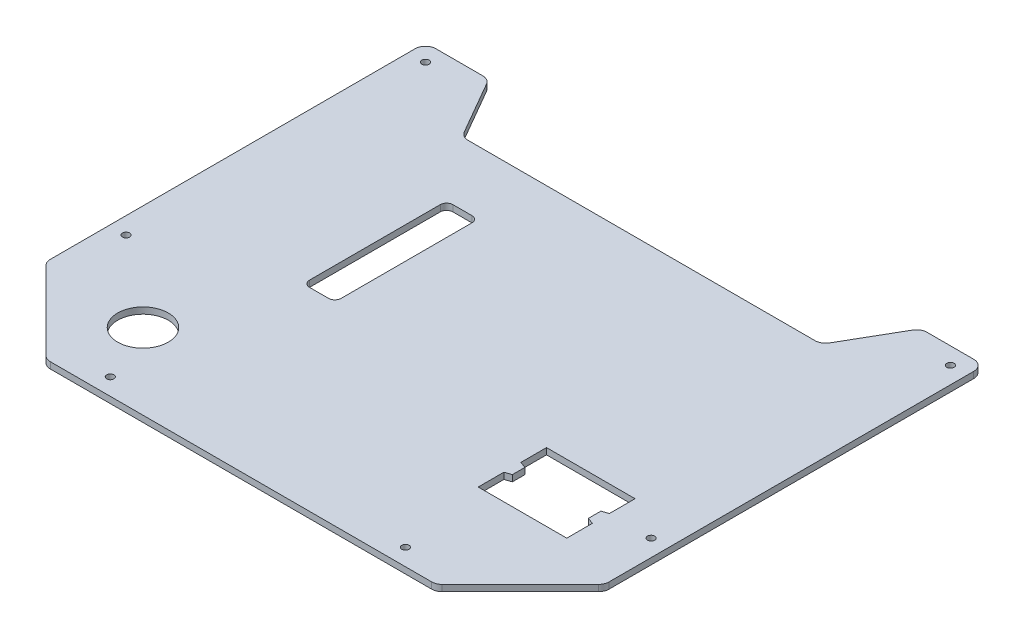
SolidWorks part; units mm, degrees
material "Acier non allié"
ref_plane "Front" through (0, 0, 0) normal (0, 0, 1) x (1, 0, 0)
ref_plane "Top" through (0, 0, 0) normal (0, 1, 0) x (1, 0, 0)
ref_plane "Right" through (0, 0, 0) normal (1, 0, 0) x (0, 0, -1)
sketch "Esquisse1" plane through (0, 0, 0) normal (0, 1, 0) x (1, 0, 0)
  line L0 (0, 0) -> (0, 1919.0564) construction
  line L1 (-92.5, 0) -> (92.5, 0)
  line L2 (92.5, 0) -> (132.5, 40)
  line L3 (132.5, 40) -> (132.5, 220)
  line L4 (132.5, 220) -> (102.5, 220)
  line L5 (102.5, 220) -> (85.1795, 190)
  line L6 (85.1795, 190) -> (-85.1795, 190)
  line L7 (-102.5, 220) -> (-85.1795, 190)
  line L8 (-132.5, 220) -> (-102.5, 220)
  line L9 (-132.5, 40) -> (-132.5, 220)
  line L10 (-92.5, 0) -> (-132.5, 40)
  point P12 (0, 190)
  dimension "D1" = 132.5
  dimension "D2" = 220
  dimension "D3" = 30
  dimension "D4" = 30
  dimension "D5" = 40
  dimension "D6" = 40
  dimension "D7" = 60
extrude "Boss.-Extru.1" add sketch "Esquisse1" along normal blind 3
fillet "Congé1" radius 5 10 edges at (132.5, 1.5, -220) (102.5, 1.5, -220) (85.1795, 1.5, -190) (-85.1795, 1.5, -190) (-102.5, 1.5, -220) (-132.5, 1.5, -220) (-132.5, 1.5, -40) (-92.5, 1.5, 0) (92.5, 1.5, 0) (132.5, 1.5, -40)
sketch "Esquisse2" plane through (0, 0, 0) normal (0, -1, 0) x (1, 0, 0)
  line L0 (0, 0) -> (0, -330.9968) construction
  line L1 (-90.4289, 0) -> (90.4289, 0) construction
  line L2 (-105.3868, -220) -> (-127.5, -220) construction
  line L3 (-132.5, -215) -> (-132.5, -42.0711) construction
  circle A0 centre (-70, -8) radius 1
  circle A1 centre (-124.5, -70) radius 1
  circle A2 centre (-124.5, -212) radius 1
  circle A3 centre (124.5, -212) radius 1
  circle A4 centre (124.5, -70) radius 1
  circle A5 centre (70, -8) radius 1
  dimension "D3" = 2
  dimension "D6" = 2
  dimension "D9" = 2
  dimension "D1" = 70
  dimension "D2" = 8
  dimension "D4" = 124.5
  dimension "D5" = 70
  dimension "D7" = 8
  dimension "D8" = 8
extrude "Enlèv. mat.-Extru.1" cut sketch "Esquisse2" against normal through all
hole_wizard "Dégagement M31" positions "Esquisse3" profile "Esquisse4" hole size "M3" standard "ISO" end condition through all
sketch "Esquisse3" plane through (0, 0, 0) normal (0, -1, 0) x (-1, 0, 0)
  point P0 (-70, 8)
  point P3 (-124.5, 70)
  point P6 (-124.5, 212)
  point P9 (124.5, 212)
  point P12 (124.5, 70)
  point P15 (70, 8)
sketch "Esquisse4" plane through (70, 0, -8) normal (1, 0, 0) x (0, 0, -1)
  line L0 (0, 0) -> (0, 3)
  line L1 (0, 3) -> (1.7, 3)
  line L2 (1.7, 3) -> (1.7, 0)
  line L5 (1.7, 0) -> (0, 0)
  line L11 (0, -6.35) -> (0, 107.95) construction
  dimension "Diamètre du perçage jusqu'au prochain" = 3.4
  dimension "Profondeur du perçage jusqu'au prochain" = 3
sketch "Esquisse5" plane through (0, 0, 0) normal (0, -1, 0) x (1, 0, 0)
  line L0 (132.5, -42.0711) -> (132.5, -215) construction
  line L1 (104.5, -82.4) -> (62.5, -82.4) construction
  line L2 (104.5, -82.4) -> (104.5, -50) construction
  line L3 (104.5, -50) -> (62.5, -50) construction
  line L4 (62.5, -82.4) -> (62.5, -50) construction
  line L5 (-90.4289, 0) -> (90.4289, 0) construction
  line L6 (83.5, -82.4) -> (83.5, -41.1293) construction
  line L7 (104.5, -66.2) -> (27.496, -66.2) construction
  line L8 (104.5, -50) -> (62.5, -50)
  line L9 (62.5, -50) -> (62.5, -62.2)
  line L10 (62.5, -62.2) -> (65.5, -63.2)
  line L11 (65.5, -63.2) -> (65.5, -69.2)
  line L12 (101.5, -63.2) -> (101.5, -69.2)
  line L13 (104.5, -62.2) -> (101.5, -63.2)
  line L14 (104.5, -50) -> (104.5, -62.2)
  line L15 (62.5, -70.2) -> (65.5, -69.2)
  line L16 (62.5, -82.4) -> (62.5, -70.2)
  line L17 (104.5, -82.4) -> (62.5, -82.4)
  line L18 (104.5, -70.2) -> (101.5, -69.2)
  line L19 (104.5, -82.4) -> (104.5, -70.2)
  line L20 (-132.5, -215) -> (-132.5, -42.0711) construction
  line L21 (-90.4289, 0) -> (90.4289, 0) construction
  line L22 (-105.3868, -220) -> (-127.5, -220) construction
  line L23 (-62.5, -160) -> (-47.5, -160)
  line L24 (-62.5, -160) -> (-62.5, -92)
  line L25 (-62.5, -92) -> (-47.5, -92)
  line L26 (-47.5, -160) -> (-47.5, -92)
  circle A0 centre (-82.5, -36) radius 12
  point P19 (83.5, -50)
  point P21 (65.5, -66.2)
  point P23 (101.5, -66.2)
  point P35 (-62.5, -126)
  dimension "D10" = 24
  dimension "D1" = 32.4
  dimension "D2" = 42
  dimension "D3" = 28
  dimension "D4" = 50
  dimension "D5" = 3
  dimension "D6" = 3
  dimension "D7" = 4
  dimension "D8" = 50
  dimension "D9" = 36
  dimension "D11" = 60
  dimension "D12" = 68
  dimension "D13" = 70
  dimension "D14" = 15
extrude "Enlèv. mat.-Extru.2" cut sketch "Esquisse5" against normal through all
fillet "Congé2" radius 3 4 edges at (-62.5, 1.5, -92) (-47.5, 1.5, -92) (-47.5, 1.5, -160) (-62.5, 1.5, -160)
equation "\"WIDTH\"= 300mm'Total width of the robot"
equation "\"LENGTH\"= 220mm'Total length of the robot"
equation "\"CUT_DEPTH\"= 45mm'Depth of the cut on the edges of the plate"
equation "\"Plate_th\"= 3mm'Thickness of the plate"
equation "\"D1\"= \"Plate_th\""
